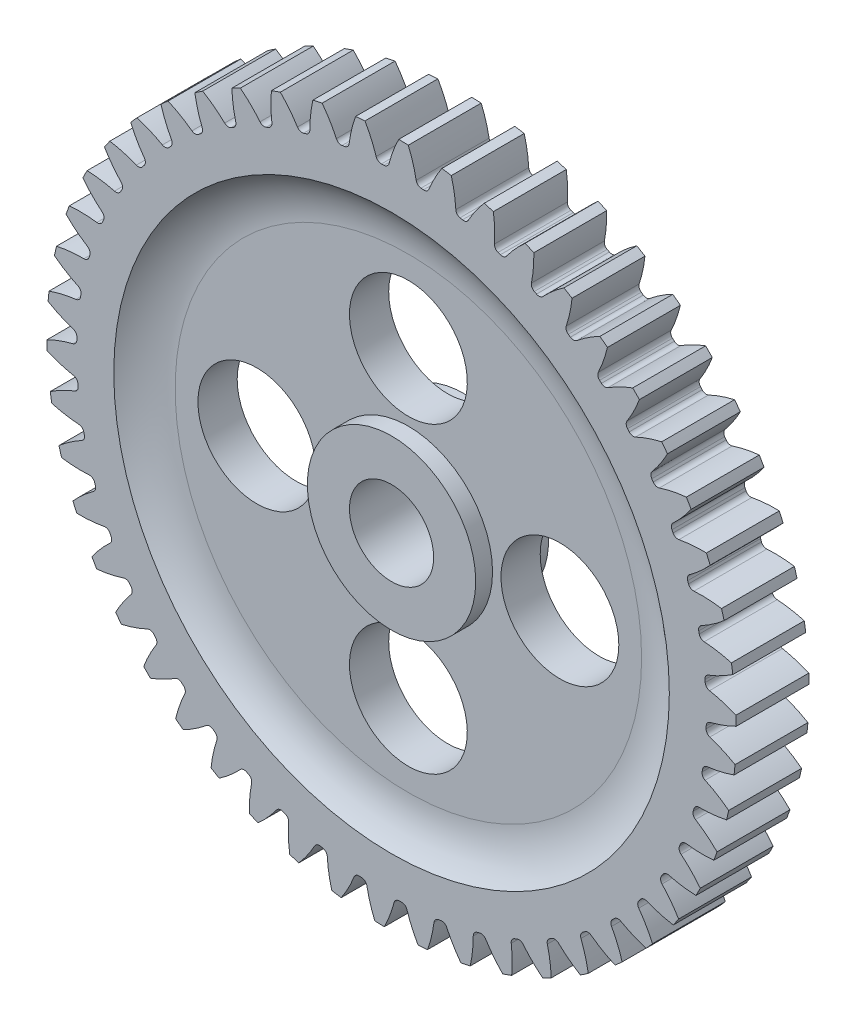
SolidWorks part; units mm, degrees
material "ABS"
ref_plane "Front" through (0, 0, 0) normal (0, 0, 1) x (1, 0, 0)
ref_plane "Top" through (0, 0, 0) normal (0, 1, 0) x (1, 0, 0)
ref_plane "Right" through (0, 0, 0) normal (1, 0, 0) x (0, 0, -1)
sketch "Sketch3" plane through (0, 0, 0) normal (0, 0, 1) x (1, 0, 0)
  circle A0 centre (0, 0) radius 26
  dimension "od" = 52
extrude "gearBody" add sketch "Sketch3" along normal blind 5.5
sketch "Sketch2" plane through (0, 0, 0) normal (0, 0, 1) x (1, 0, 0)
  line L0 (0, 0) -> (21.7041, 8.9901) construction
  line L1 (29.3392, -5.6152) -> (0, 0) construction
  line L2 (0, 0) -> (36.3143, 0) construction
  line L3 (24.9999, -0.0564) -> (24.9435, -1.6792) construction
  line L5 (24.9717, -0.8678) -> (0, 0) construction
  line L7 (0, 0) -> (23.4923, 0) construction
  arc A0 (23.4876, -0.4715) -> (23.4636, -1.1602) centre (0, 0) ccw construction
  arc A1 (25.9973, 0.3721) -> (25.9088, -2.1759) centre (0, 0) ccw construction
  arc A2 (24.9999, -0.0564) -> (24.9435, -1.6792) centre (0, 0) ccw construction
  arc A3 (23.7314, -0.9194) -> (23.738, -0.7303) centre (0, 0) ccw
  arc A4 (29.3392, -5.6152) -> (24.0111, -1.3208) centre (21.0276, -10.4751) ccw
  arc A5 (29.3392, -5.6152) -> (29.6583, 3.5649) centre (0, 0) ccw
  arc A6 (29.6583, 3.5649) -> (24.0448, -0.3492) centre (21.7041, 8.9901) cw
  arc A7 (23.738, -0.7303) -> (24.0448, -0.3492) centre (24.1435, -0.7428) cw
  arc A8 (24.0111, -1.3208) -> (23.7314, -0.9194) centre (24.1368, -0.9351) cw
  point P6 (29.6583, 3.5649)
  point P22 (29.3392, -5.6152)
  dimension "baseDia" = 46.9846
  dimension "od" = 52
  dimension "pd" = 50
  dimension "rd" = 47.4984
  dimension "rFillet" = 0.4057
  dimension "pointX" = 29.6583
  dimension "pointY" = 3.5649
  dimension "CTT" = 1.6228
  dimension "flankCenterAngle" = 22.5
extrude "toothCut" cut sketch "Sketch2" along normal through all
pattern_circular "CirPattern1" count 50 over 360 about axis through (0, 0, 5.5) along (0, 0, -1) of "toothCut"
ref_axis "toothSpace" through (0, 0, 0) along (0.9994, -0.0347, 0)
ref_axis "Axis2" through (25.8763, -2.5328, 0) along (-0.9952, 0.0974, 0)
sketch "boreDia" plane through (0, 0, 0) normal (0, 0, 1) x (1, 0, 0)
  circle A0 centre (0, 0) radius 1.5875
  dimension "boreDia" = 3.175
extrude "bore" cut sketch "boreDia" against normal mid plane 25400
sketch "centerLine" plane through (0, 0, 0) normal (0, 1, 0) x (1, 0, 0)
  line L0 (0, 36.4807) -> (0, -59.6309) construction
ref_plane "CB1plane" through (0, 0, 0) normal (0, 0, -1) x (-1, 0, 0)
ref_plane "CB2plane" through (0, 0, 5.5) normal (0, 0, 1) x (1, 0, 0)
ref_axis "Axis1" through (0, 0, 50) along (0, 0, -1)
sketch "Sketch4" plane through (0, 0, 5.5) normal (0, 0, 1) x (1, 0, 0)
  circle A0 centre (0, 0) radius 20.955
  circle A1 centre (0, 0) radius 6.35
  dimension "D1" = 41.91
  dimension "D2" = 12.7
extrude "Cut-Extrude1" cut sketch "Sketch4" against normal blind 1.27
sketch "Sketch5" plane through (0, 0, 0) normal (0, 0, -1) x (-1, 0, 0)
  circle A0 centre (0, 0) radius 6.35
  circle A1 centre (0, 0) radius 20.955
  dimension "D1" = 12.7
  dimension "D2" = 41.91
extrude "Cut-Extrude2" cut sketch "Sketch5" against normal blind 1.27
fillet "Fillet2" radius 5.08 2 edges at (-20.955, 0, 1.27) (20.955, 0, 4.23)
sketch "Sketch6" plane through (0, 0, 4.23) normal (0, 0, 1) x (1, 0, 0)
  circle A0 centre (11.43, 0) radius 4.445
  dimension "D1" = 8.89
  dimension "D2" = 11.43
extrude "Cut-Extrude3" cut sketch "Sketch6" against normal through all
pattern_circular "CirPattern2" count 4 every 90 about axis through (0, 0, -12700) along (0, 0, 1) of "Cut-Extrude3"
sketch "Sketch7" plane through (0, 0, 5.5) normal (0, 0, 1) x (1, 0, 0)
  circle A0 centre (0, 0) radius 3.175
  dimension "D1" = 6.35
extrude "Cut-Extrude4" cut sketch "Sketch7" against normal up to next
